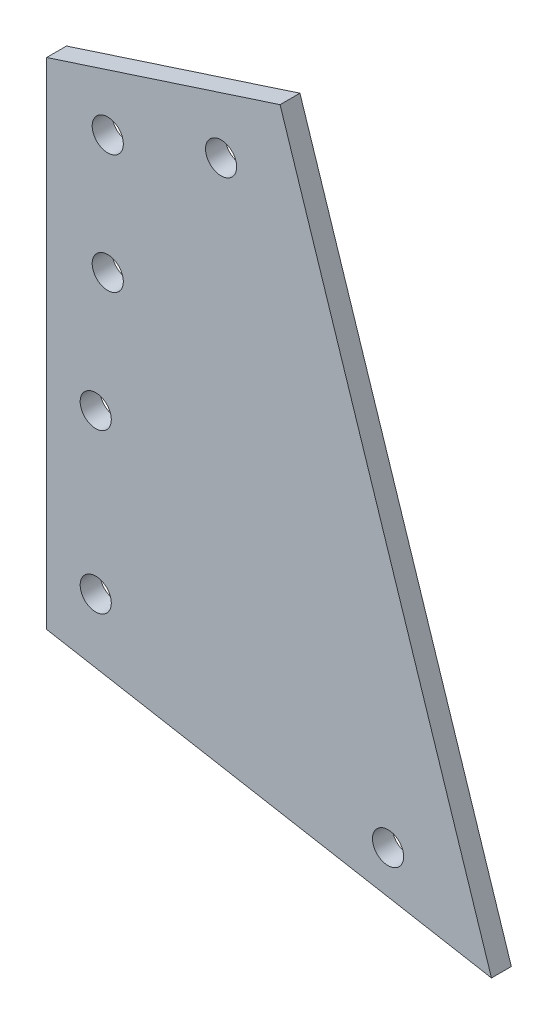
SolidWorks part; units mm, degrees
ref_plane "Front Plane" through (0, 0, 0) normal (0, 0, 1) x (1, 0, 0)
ref_plane "Top Plane" through (0, 0, 0) normal (0, 1, 0) x (1, 0, 0)
ref_plane "Right Plane" through (0, 0, 0) normal (1, 0, 0) x (0, 0, -1)
sketch "Sketch2" plane through (0, 0, 0) normal (0, 0, 1) x (1, 0, 0)
  line L0 (40.992, 298.8407) -> (42.1693, 295.2171) construction
  line L2 (40.992, 298.8407) -> (52.5693, 263.2093) construction
  line L6 (201.5046, -195.1666) -> (40.992, 298.8407) construction
  line L7 (75.9661, 191.2015) -> (42.1693, 295.2171)
  line L8 (4.8542, 283.0927) -> (4.8542, 203.9015)
  line L9 (4.8542, 203.9015) -> (75.9661, 191.2015)
  line L10 (12.7, 238.125) -> (12.7, 212.725) construction
  line L11 (52.6739, 180.6913) -> (64.7523, 184.6158) construction
  line L12 (177.3478, -203.0157) -> (25.4, 264.6316) construction
  line L13 (64.7523, 184.6158) -> (29.6006, 292.8015) construction
  line L14 (42.1693, 295.2171) -> (4.8542, 283.0927)
  point P6 (0, 0)
  point P8 (0, 0)
  dimension "D1" = 109.3686
extrude "Boss-Extrude1" add sketch "Sketch2" along normal blind 3.175
sketch "Sketch3" plane through (0, 0, 3.175) normal (0, 0, 1) x (1, 0, 0)
  line L0 (75.9661, 191.2015) -> (63.8876, 187.2769) construction
  line L1 (63.8876, 187.2769) -> (29.6006, 292.8015) construction
  line L3 (61.7899, 193.7332) -> (59.4352, 200.9803) construction
  line L4 (4.8542, 203.9015) -> (75.9661, 191.2015) construction
  line L5 (29.6006, 292.8015) -> (32.7403, 283.1387) construction
  line L6 (32.7403, 283.1387) -> (14.6226, 277.2519) construction
  line L7 (14.6226, 277.2519) -> (14.6226, 258.2019) construction
  point P10 (0, 0)
  dimension "D1" = 86.3865
hole_wizard "#10 Clearance Hole1" positions "Sketch4" profile "Sketch5" hole size "#10" standard "ANSI Inch" end condition through all
sketch "Sketch4" plane through (0, 0, 3.175) normal (0, 0, 1) x (1, 0, 0)
  point P0 (32.7403, 283.1387)
  point P3 (59.4352, 200.9803)
  point P7 (12.7, 238.125)
  point P10 (12.7, 212.725)
  point P14 (14.6226, 277.2519)
  point P17 (14.6226, 258.2019)
sketch "Sketch5" plane through (32.7403, 283.1387, 3.175) normal (1, 0, 0) x (0, -1, 0)
  line L0 (0, 0) -> (0, 3.175)
  line L1 (0, 3.175) -> (2.4892, 3.175)
  line L2 (2.4892, 3.175) -> (2.4892, 0)
  line L5 (2.4892, 0) -> (0, 0)
  line L11 (0, -6.35) -> (0, 107.95) construction
  dimension "Thru Hole Dia." = 4.9784
  dimension "Thru Hole Depth" = 3.175
